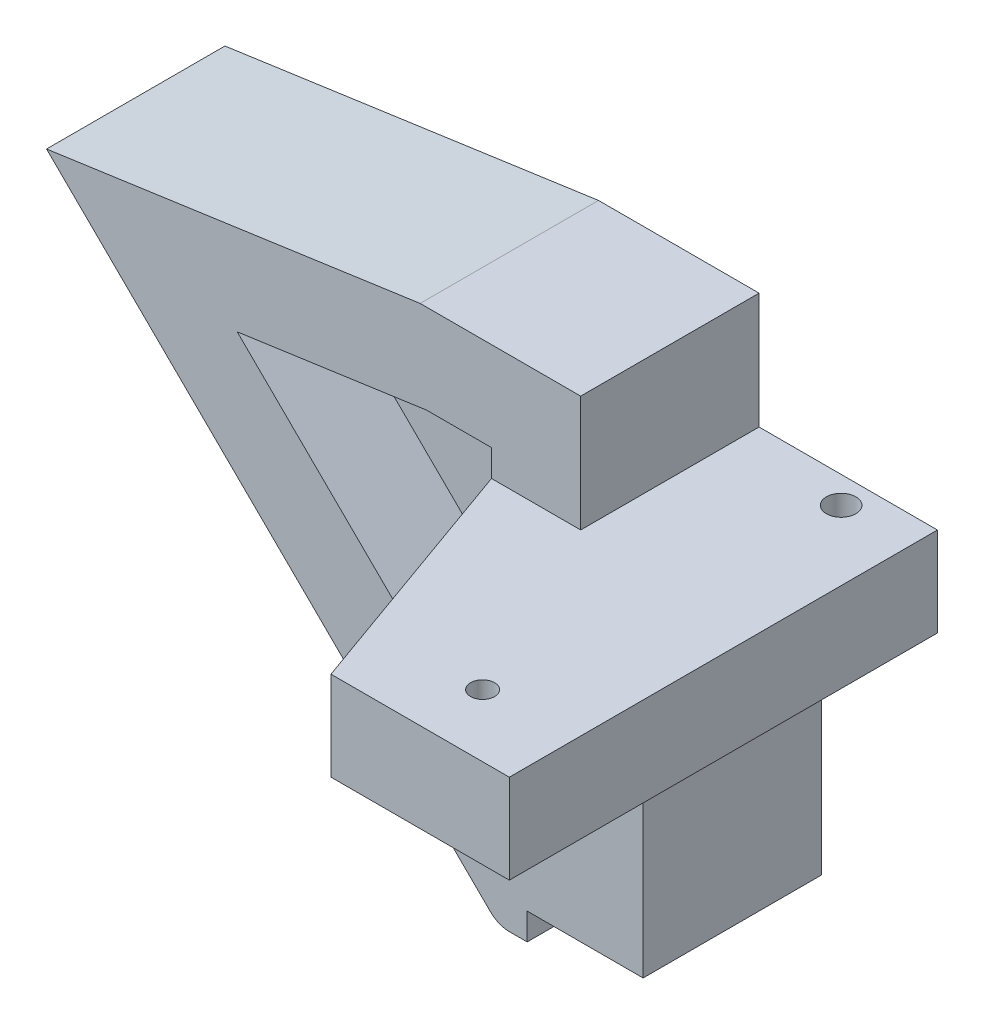
SolidWorks part; units mm, degrees
ref_plane "Front" through (0, 0, 0) normal (0, 0, 1) x (1, 0, 0)
ref_plane "Top" through (0, 0, 0) normal (0, 1, 0) x (1, 0, 0)
ref_plane "Right" through (0, 0, 0) normal (1, 0, 0) x (0, 0, -1)
sketch "草图1" plane through (0, 0, 0) normal (0, 0, 1) x (1, 0, 0)
  line L0 (0, 0) -> (0, 40)
  line L1 (0, 40) -> (-5, 40)
  line L2 (0, 0) -> (-5, 0)
  line L3 (-5, 0) -> (-5, -3)
  line L4 (-5, -3) -> (-13, -3)
  line L5 (-5, 53) -> (-23, 53)
  line L6 (-5, 40) -> (-5, 53)
  line L8 (-15.1213, -2.1213) -> (-64.8886, 47.0507)
  line L10 (-23, 53) -> (-64.8886, 47.0507)
  arc A0 (-15.1213, -2.1213) -> (-13, -3) centre (-13, 0) ccw
extrude "凸台-拉伸1" add sketch "草图1" along normal blind 172
shell "抽壳1" thickness 6
sketch "草图2" plane through (0, 0, 0) normal (1, 0, 0) x (0, 0, -1)
  line L1 (-154, 2) -> (-154, 18)
  line L2 (-154, 18) -> (-118, 18)
  line L3 (-118, 18) -> (-118, 2)
  line L4 (-54, 2) -> (-54, 18)
  line L5 (-54, 18) -> (-18, 18)
  line L6 (-18, 2) -> (-18, 18)
  line L7 (-54, 2) -> (-18, 2)
  line L9 (-154, 2) -> (-118, 2)
extrude "切除-拉伸1" cut sketch "草图2" against normal blind 74
ref_plane "基准面1" through (0, 0, 86) normal (0, 0, -1) x (-1, 0, 0)
sketch "草图3" plane through (0, 0, 86) normal (0, 0, -1) x (-1, 0, 0)
  line L0 (5, 53) -> (5, 40)
  line L1 (5, 40) -> (0, 40)
  line L2 (0, 40) -> (0, 0)
  line L3 (0, 0) -> (5, 0)
  line L4 (5, 0) -> (5, -3)
  line L5 (5, -3) -> (13, -3)
  line L6 (13, -3) -> (16.5794, -0.6807)
  line L7 (64.8886, 47.0507) -> (15.1213, -2.1213) construction
  line L8 (16.5794, -0.6807) -> (64.8886, 47.0507)
  line L9 (64.8886, 47.0507) -> (23, 53)
  line L10 (23, 53) -> (5, 53)
extrude "凸台-拉伸2" add sketch "草图3" along normal mid plane 4 contours L8 L9 L10 L0 L1 L2 L3 L4 L5 L6
sketch "草图4" plane through (0, 0, 172) normal (0, 0, 1) x (1, 0, 0)
  circle A0 centre (-15, 21.0713) radius 10
extrude "切除-拉伸2" cut sketch "草图4" against normal blind 186
sketch "草图5" plane through (0, 53, 0) normal (0, 1, 0) x (1, 0, 0)
  circle A1 centre (-13.3382, -63.5) radius 1.5
  circle A2 centre (-13.3382, -108.5) radius 1.5
extrude "切除-拉伸3" cut sketch "草图5" against normal blind 10
sketch "草图6" plane through (0, 0, 172) normal (0, 0, 1) x (1, 0, 0)
  line L0 (-11, 6) -> (-14.8042, 6)
  line L1 (-52.062, 42.8122) -> (-11.7678, 3) construction
  line L2 (-14.8042, 6) -> (-11.7678, 3)
  line L3 (-11.7678, 3) -> (-11, 3)
  line L4 (-11, 3) -> (-11, 6)
extrude "凸台-拉伸3" add sketch "草图6" against normal blind 172
sketch "草图7" plane through (0, 0, 0) normal (1, 0, 0) x (0, 0, -1)
  line L0 (-154, 18) -> (-154, 2)
  line L1 (-154, 2) -> (-118, 2)
  line L2 (-118, 2) -> (-118, 18)
  line L3 (-118, 18) -> (-154, 18)
  line L4 (-54, 18) -> (-54, 2)
  line L5 (-54, 2) -> (-18, 2)
  line L6 (-18, 2) -> (-18, 18)
  line L7 (-18, 2) -> (-18, 18) construction
  line L8 (-18, 18) -> (-54, 18) construction
  line L9 (-18, 18) -> (-54, 18)
extrude "切除-拉伸4" cut sketch "草图7" against normal blind 172
sketch "草图8" plane through (0, -3, 0) normal (0, -1, 0) x (1, 0, 0)
  line L0 (-5, 172) -> (-11, 172)
  line L1 (-13, 172) -> (-5, 172) construction
  line L2 (-11, 172) -> (-11, 0)
  line L3 (-13, 0) -> (-5, 0) construction
  line L4 (-11, 0) -> (-5, 0)
  line L5 (-5, 0) -> (-5, 172)
extrude "切除-拉伸5" cut sketch "草图8" against normal blind 3
sketch "草图9" plane through (0, 0, 0) normal (1, 0, 0) x (0, 0, -1)
  line L0 (-86, 40) -> (-151, 40)
  line L1 (-172, 40) -> (0, 40) construction
  line L2 (-151, 40) -> (-151, 35)
  line L3 (-151, 35) -> (-86, 35)
  line L4 (-86, -55) -> (-86, 55) construction
  line L5 (-86, 35) -> (-21, 35)
  line L6 (-21, 35) -> (-21, 40)
  line L7 (-21, 40) -> (-86, 40)
extrude "凸台-拉伸4" add sketch "草图9" along normal blind 15
chamfer "倒角1" distance 15 angle 45 1 edges at (15, 37.5, 151)
chamfer "倒角2" distance 15 angle 45 1 edges at (15, 37.5, 21)
chamfer "倒角3" distance 8 angle 45 1 edges at (0, 35, 86)
sketch "草图10" plane through (0, 0, 0) normal (0, -1, 0) x (1, 0, 0)
  circle A2 centre (-5, 158) radius 1.35
  circle A3 centre (-5, 111) radius 1.35
  circle A4 centre (-5, 61) radius 1.35
  circle A5 centre (-5, 14.0136) radius 1.35
extrude "切除-拉伸6" cut sketch "草图10" against normal blind 15
sketch "草图12" plane through (0, 40, 0) normal (0, 1, 0) x (1, 0, 0)
  line L2 (55, -86) -> (-55, -86) construction
  circle A1 centre (5, -41) radius 1.35
  circle A2 centre (5, -86) radius 1.35
  circle A3 centre (5, -131) radius 1.35
extrude "切除-拉伸7" cut sketch "草图12" against normal blind 15
sketch "草图14" plane through (0, 0, 0) normal (1, 0, 0) x (0, 0, -1)
  line L0 (-83.1596, 53) -> (-83.1596, -3)
  line L1 (-172, 53) -> (0, 53) construction
  line L2 (-172, -3) -> (0, -3) construction
  line L3 (-83.1596, -3) -> (-68.1596, -3)
  line L4 (-68.1596, -3) -> (-68.1596, 53)
  line L5 (-68.1596, 53) -> (-83.1596, 53)
extrude "切除-拉伸8" cut sketch "草图14" against normal mid plane 165 flip side to cut
sketch "草图15" plane through (0, 0, 68.1596) normal (0, 0, -1) x (-1, 0, 0)
  line L0 (0, 0) -> (-2, 0)
  line L1 (-2, 0) -> (-2, 29)
  line L2 (-8, 35) -> (0, 27) construction
  line L3 (-2, 29) -> (0, 27)
  line L4 (0, 27) -> (0, 0)
extrude "凸台-拉伸5" add sketch "草图15" against normal blind 15
sketch "草图16" plane through (0, 0, 68.1596) normal (0, 0, -1) x (-1, 0, 0)
  line L0 (-2, 29) -> (-2, 35)
  line L1 (-8, 35) -> (-2, 35)
  line L2 (-8, 35) -> (-2, 29)
extrude "切除-拉伸9" cut sketch "草图16" against normal blind 15
sketch "草图17" plane through (0, 0, 68.1596) normal (0, 0, -1) x (-1, 0, 0)
  line L0 (-15, 35) -> (-15, 30)
  line L1 (-15, 30) -> (-2, 30)
  line L2 (-2, 35) -> (-2, 0) construction
  line L3 (-2, 30) -> (-2, 35)
  line L4 (-2, 35) -> (-15, 35)
extrude "凸台-拉伸6" add sketch "草图17" against normal blind 15
sketch "草图18" plane through (0, 0, 68.1596) normal (0, 0, -1) x (-1, 0, 0)
  line L0 (-15, 40) -> (-15, 30)
  line L1 (-15, 30) -> (-2, 30)
  line L2 (-2, 30) -> (-2, 0)
  line L3 (-2, 0) -> (11, 0)
  line L4 (11, 0) -> (11, -3)
  line L5 (11, -3) -> (13, -3)
  line L6 (15.1213, -2.1213) -> (64.8886, 47.0507)
  line L7 (64.8886, 47.0507) -> (23, 53)
  line L8 (23, 53) -> (5, 53)
  line L9 (5, 53) -> (5, 40)
  line L10 (5, 40) -> (-15, 40)
  arc A0 (13, -3) -> (15.1213, -2.1213) centre (13, 0) ccw
extrude "凸台-拉伸7" add sketch "草图18" against normal blind 20 contours L10 L0 L1 L2 L3 L4 L5 A0 L6 L7 L8 L9
shell "抽壳2" thickness 10 removed face at (-9.5081, 23.7265, 88.1596)
sketch "草图20" plane through (0, 0, 88.1596) normal (0, 0, 1) x (1, 0, 0)
  line L0 (15, 40) -> (-15, 40)
  line L1 (-15, 43) -> (-15, 30) construction
  line L2 (-15, 40) -> (-15, 30)
  line L3 (-15, 30) -> (-8, 30)
  line L4 (-8, 30) -> (-8, 10) construction
  line L5 (-8, 30) -> (-8, 10) construction
  line L6 (-8, 30) -> (-8, 22)
  line L7 (-8, 22) -> (2, 22)
  line L8 (2, 30) -> (2, 0) construction
  line L9 (2, 22) -> (2, 30)
  line L10 (2, 30) -> (15, 30)
  line L11 (15, 30) -> (15, 40)
extrude "凸台-拉伸8" add sketch "草图20" along normal blind 28
sketch "草图21" plane through (2, 0, 0) normal (1, 0, 0) x (0, 0, -1)
  line L0 (-116.1596, 30) -> (-88.1596, 22)
  line L1 (-88.1596, 22) -> (-116.1596, 22)
  line L2 (-116.1596, 22) -> (-116.1596, 30)
extrude "切除-拉伸10" cut sketch "草图21" against normal blind 20
sketch "草图22" plane through (0, 40, 0) normal (0, 1, 0) x (1, 0, 0)
  line L1 (-8, -116.1596) -> (-15, -116.1596)
  line L2 (-15, -116.1596) -> (-15, -88.1596)
  line L4 (15, -116.1596) -> (-15, -116.1596) construction
  line L5 (-5, -116.1596) -> (-8, -116.1596)
  line L6 (-5, -116.1596) -> (-15, -88.1596)
extrude "切除-拉伸11" cut sketch "草图22" against normal blind 20
sketch "草图23" plane through (0, 40, 0) normal (0, 1, 0) x (1, 0, 0)
  circle A0 centre (7.2, -71.1596) radius 1.65
  circle A1 centre (5, -109.1596) radius 1.35
extrude "切除-拉伸12" cut sketch "草图23" against normal blind 22
sketch "草图26" plane through (0, 0, 0) normal (0, -1, 0) x (1, 0, 0)
  circle A0 centre (-5, 78.1596) radius 1.35
extrude "切除-拉伸14" cut sketch "草图26" against normal blind 10
